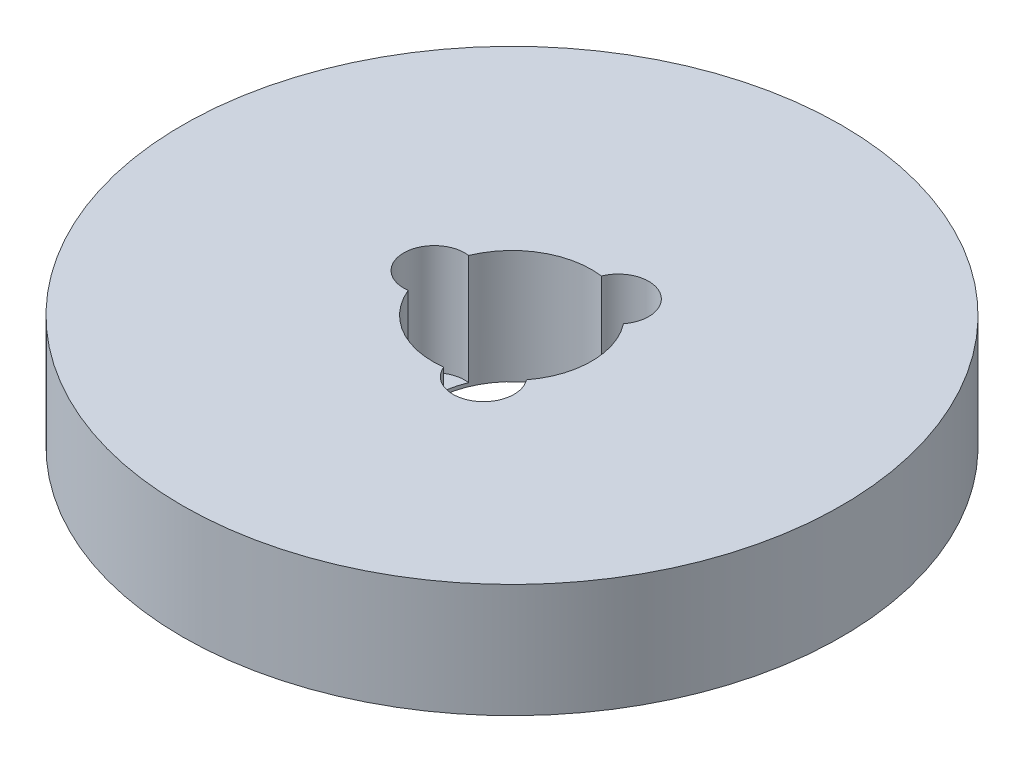
SolidWorks part; units mm, degrees
ref_plane "Front Plane" through (0, 0, 0) normal (0, 0, 1) x (1, 0, 0)
ref_plane "Top Plane" through (0, 0, 0) normal (0, 1, 0) x (1, 0, 0)
ref_plane "Right Plane" through (0, 0, 0) normal (1, 0, 0) x (0, 0, -1)
sketch "Sketch1" plane through (0, 0, 0) normal (0, 1, 0) x (1, 0, 0)
  circle A0 centre (0, 0) radius 72.5
  dimension "FLANGE_OD" = 145
extrude "Boss-Extrude1" add sketch "Sketch1" along normal blind 25
sketch "Sketch2" plane through (0, 0, 0) normal (0, 1, 0) x (1, 0, 0)
  circle A0 centre (0, 0) radius 17.5
  dimension "BORE_D" = 35
extrude "Cut-Extrude1" cut sketch "Sketch2" along normal through all
sketch "Sketch3" plane through (0, 25, 0) normal (0, 1, 0) x (1, 0, 0)
  circle A0 centre (0, 0) radius 17.1046 construction
  circle A1 centre (-17.1046, 0) radius 6.7218
  dimension "BOLT_D" = 13.4435
  dimension "BOLT_PCD" = 34.2092
extrude "Cut-Extrude2" cut sketch "Sketch3" against normal blind 24.2346
pattern_circular "CirPattern1" count 3 over 360 about axis through (0, 0, 0) along (0, 1, 0) of "Cut-Extrude2"
